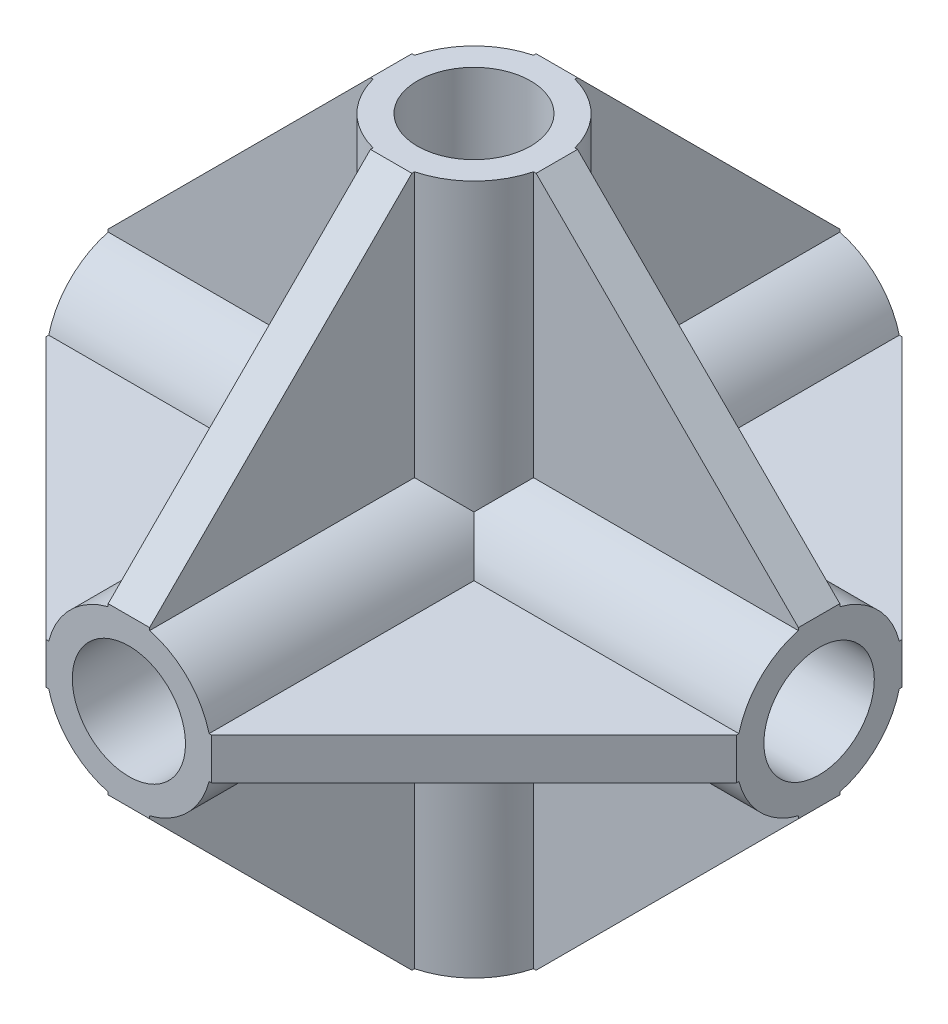
SolidWorks part; units mm, degrees
ref_plane "前视基准面" through (0, 0, 0) normal (0, 0, 1) x (1, 0, 0)
ref_plane "上视基准面" through (0, 0, 0) normal (0, 1, 0) x (1, 0, 0)
ref_plane "右视基准面" through (0, 0, 0) normal (1, 0, 0) x (0, 0, -1)
sketch "草图1" plane through (0, 0, 0) normal (0, 1, 0) x (1, 0, 0)
  circle A0 centre (0, 0) radius 4.1
  circle A1 centre (0, 0) radius 6
  dimension "D1" = 8.2
  dimension "D2" = 12
extrude "凸台-拉伸1" add sketch "草图1" along normal mid plane 50
sketch "草图2" plane through (0, 0, 0) normal (0, 0, 1) x (1, 0, 0)
  circle A0 centre (0, 0) radius 6
  circle A1 centre (0, 0) radius 4.1
  dimension "D1" = 8.2
  dimension "D2" = 12
extrude "凸台-拉伸2" add sketch "草图2" along normal mid plane 50
sketch "草图3" plane through (0, 0, 0) normal (1, 0, 0) x (0, 0, -1)
  circle A0 centre (0, 0) radius 6
  circle A1 centre (0, 0) radius 4
  dimension "D1" = 12
  dimension "D2" = 8
extrude "凸台-拉伸3" add sketch "草图3" along normal mid plane 50
sketch "草图4" plane through (0, -25, 0) normal (0, -1, 0) x (1, 0, 0)
  circle A0 centre (0, 0) radius 4.1
extrude "切除-拉伸1" cut sketch "草图4" against normal blind 44
sketch "草图5" plane through (-25, 0, 0) normal (-1, 0, 0) x (0, 0, 1)
  circle A0 centre (0, 0) radius 4
extrude "切除-拉伸2" cut sketch "草图5" against normal blind 44
sketch "草图6" plane through (0, 0, -25) normal (0, 0, -1) x (-1, 0, 0)
  circle A0 centre (0, 0) radius 4.1
extrude "切除-拉伸3" cut sketch "草图6" against normal blind 44
ref_plane "基准面4" through (0, 6, 0) normal (0, 1, 0) x (1, 0, 0)
sketch "草图7" plane through (0, 6, 0) normal (0, 1, 0) x (1, 0, 0)
  circle A0 centre (0, 0) radius 5.5
extrude "凸台-拉伸4" add sketch "草图7" along normal blind 2
ref_plane "基准面5" through (6, 0, 0) normal (1, 0, 0) x (0, 0, -1)
sketch "草图8" plane through (6, 0, 0) normal (1, 0, 0) x (0, 0, -1)
  circle A0 centre (0, 0) radius 5.5
extrude "凸台-拉伸5" add sketch "草图8" along normal blind 2
sketch "草图11" plane through (0, 0, 0) normal (1, 0, 0) x (0, 0, -1)
  line L0 (-6, 25) -> (-25, 6)
  line L1 (27.5, 6) -> (-27.5, 6) construction
  line L2 (-25, 6) -> (-25, -6) construction
  line L3 (-25, 6) -> (-25, -6)
  line L4 (-25, -6) -> (-6, -25)
  line L5 (-6, -25) -> (6, -25) construction
  line L6 (-6, -25) -> (6, -25)
  line L7 (6, -25) -> (25, -6)
  line L8 (25, -6) -> (25, 6) construction
  line L9 (25, -6) -> (25, 6)
  line L10 (25, 6) -> (6, 25)
  line L11 (6, 25) -> (-6, 25)
extrude "凸台-拉伸6" add sketch "草图11" along normal mid plane 3
sketch "草图12" plane through (0, 0, 0) normal (0, 0, 1) x (1, 0, 0)
  line L0 (6, 25) -> (25, 6)
  line L1 (6, -27.5) -> (6, 27.5) construction
  line L2 (6, 25) -> (1.5, 25) construction
  line L3 (27.5, 6) -> (-27.5, 6) construction
  line L4 (25, -6) -> (25, 6) construction
  line L5 (25, 6) -> (25, -6)
  line L6 (25, -6) -> (6, -25)
  line L7 (1.5, -25) -> (6, -25) construction
  line L8 (6, -25) -> (-6, -25)
  line L9 (-6, -25) -> (-25, -6)
  line L10 (-25, -6) -> (-25, 6)
  line L11 (-25, 6) -> (-25, -6) construction
  line L12 (-25, 6) -> (-6, 25)
  line L13 (-6, 25) -> (6, 25)
extrude "凸台-拉伸7" add sketch "草图12" along normal mid plane 3
sketch "草图13" plane through (0, 0, 0) normal (0, 1, 0) x (1, 0, 0)
  line L0 (6, 25) -> (25, 6)
  line L1 (6, -27.5) -> (6, 27.5) construction
  line L2 (6, 25) -> (1.5, 25) construction
  line L3 (25, 6) -> (25, -6)
  line L4 (25, -6) -> (6, -25)
  line L5 (1.5, -25) -> (6, -25) construction
  line L6 (6, -25) -> (-6, -25)
  line L7 (-6, -6) -> (-6, -25) construction
  line L8 (-6, -25) -> (-25, -6)
  line L9 (-25, -1.5) -> (-25, -6) construction
  line L10 (-25, -6) -> (-25, 6)
  line L11 (-25, 6) -> (-25, 1.5) construction
  line L12 (-25, 6) -> (-6, 25)
  line L13 (-6, 25) -> (6, 25)
extrude "凸台-拉伸8" add sketch "草图13" along normal mid plane 3
sketch "草图14" plane through (0, -25, 0) normal (0, -1, 0) x (1, 0, 0)
  circle A1 centre (0, 0) radius 4.1
extrude "切除-拉伸4" cut sketch "草图14" against normal blind 86
sketch "草图15" plane through (-25, 0, 0) normal (-1, 0, 0) x (0, 0, 1)
  circle A0 centre (0, 0) radius 4
extrude "切除-拉伸5" cut sketch "草图15" against normal blind 86
sketch "草图16" plane through (0, 0, 25) normal (0, 0, 1) x (1, 0, 0)
  circle A0 centre (0, 0) radius 4.1
extrude "切除-拉伸6" cut sketch "草图16" against normal blind 86
sketch "草图17" plane through (6, 0, 0) normal (1, 0, 0) x (0, 0, -1)
  line L4 (27.5, 6) -> (-27.5, 6) construction
  line L5 (-6, 1.5) -> (-1.5, 1.5)
  line L6 (-6, 1.5) -> (-6, -1.5)
  line L7 (-6, -1.5) -> (-1.5, -1.5)
  line L8 (6, 1.5) -> (6, -1.5)
  line L9 (-1.5, -6) -> (1.5, -6)
  line L10 (-1.5, -6) -> (-1.5, -1.5)
  line L11 (-1.5, 6) -> (1.5, 6)
  line L12 (1.5, -6) -> (1.5, -1.5)
  line L13 (1.5, 6) -> (1.5, 25) construction
  line L14 (-1.5, 1.5) -> (-1.5, 6)
  line L15 (1.5, 1.5) -> (1.5, 6)
  line L16 (1.5, 1.5) -> (6, 1.5)
  line L17 (1.5, -1.5) -> (6, -1.5)
extrude "凸台-拉伸10" add sketch "草图17" along normal blind 2
sketch "草图18" plane through (0, 6, 0) normal (0, 1, 0) x (1, 0, 0)
  line L0 (6, -27.5) -> (6, 27.5) construction
  line L1 (-6, 1.5) -> (-1.5, 1.5)
  line L2 (-6, 1.5) -> (-6, -1.5)
  line L3 (-6, -1.5) -> (-1.5, -1.5)
  line L4 (6, 1.5) -> (6, -1.5)
  line L5 (5.8095, -1.5) -> (25, -1.5) construction
  line L6 (1.5, 1.5) -> (6, 1.5)
  line L7 (-1.5, 6) -> (1.5, 6)
  line L8 (-1.5, 6) -> (-1.5, 1.5)
  line L9 (-1.5, -6) -> (1.5, -6)
  line L10 (1.5, 6) -> (1.5, 1.5)
  line L11 (1.5, -1.5) -> (1.5, -6)
  line L12 (-1.5, -1.5) -> (-1.5, -6)
  line L13 (1.5, -1.5) -> (6, -1.5)
extrude "凸台-拉伸11" add sketch "草图18" along normal blind 2
